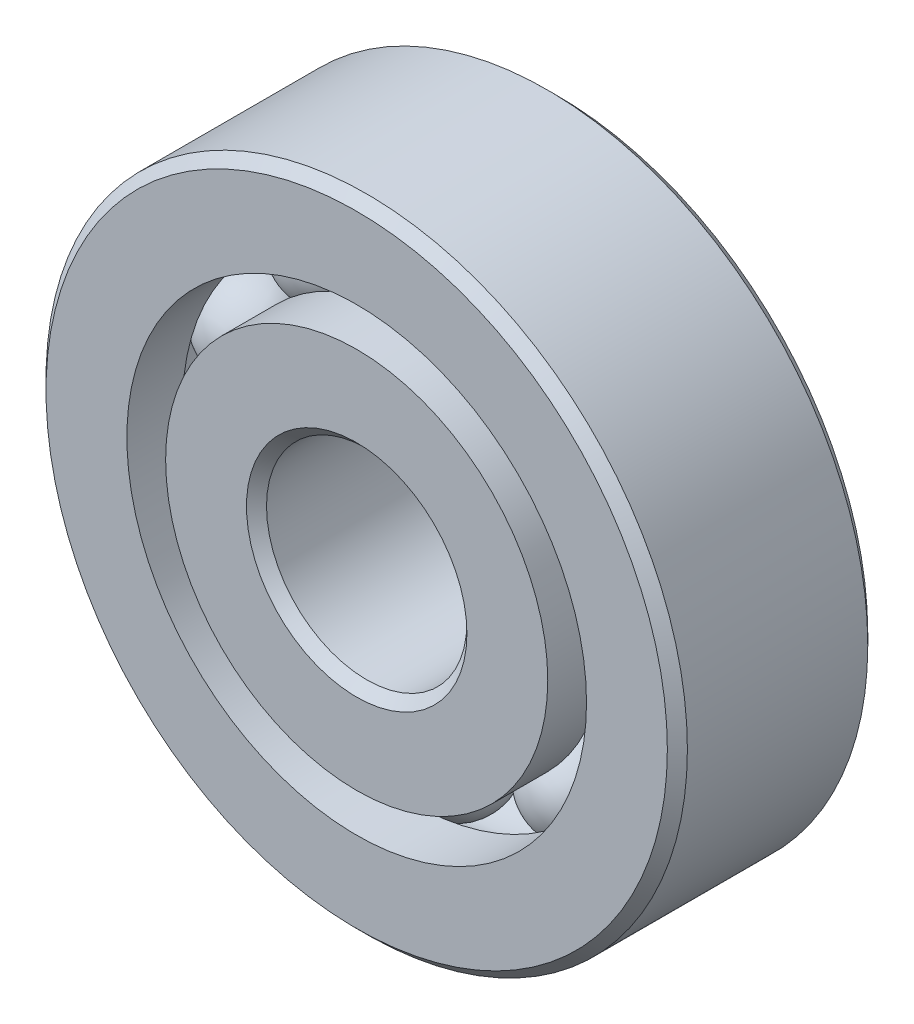
SolidWorks part; units mm, degrees
ref_plane "Front Plane" through (0, 0, 0) normal (0, 0, 1) x (1, 0, 0)
ref_plane "Top Plane" through (0, 0, 0) normal (0, 1, 0) x (1, 0, 0)
ref_plane "Right Plane" through (0, 0, 0) normal (1, 0, 0) x (0, 0, -1)
sketch "Sketch1" plane through (0, 0, 0) normal (1, 0, 0) x (0, 0, -1)
  line L0 (-2.5, 0) -> (2.5, 0) construction
  line L1 (0, 8) -> (0, -8) construction
  line L2 (2.25, 8) -> (-2.25, 8)
  line L3 (-2.25, 8) -> (-2.5, 7.75)
  line L4 (-2.5, 7.75) -> (-2.5, 5.7335)
  line L5 (-2.5, 5.7335) -> (-1.1111, 5.7335)
  line L6 (2.5, 5.7335) -> (1.1111, 5.7335)
  line L7 (2.5, 7.75) -> (2.5, 5.7335)
  line L8 (2.25, 8) -> (2.5, 7.75)
  line L9 (0, 8) -> (0, 5.25) construction
  line L10 (0, 5.25) -> (0, 2.5) construction
  arc A0 (-1.1111, 5.7335) -> (1.1111, 5.7335) centre (0, 5.25) cw
  point P14 (0, 2.5)
  dimension "Width" = 5
  dimension "OD" = 16
  dimension "D1" = 45
  dimension "D2" = 0.25
  dimension "Shaft Dia" = 5
  dimension "D3" = 2.2222
  dimension "D4" = 0.4835
revolve "Revolve1" add sketch "Sketch1" angle 360 about L0
sketch "Sketch3" plane through (0, 0, 0) normal (1, 0, 0) x (0, 0, -1)
  line L0 (-2.5, 4.7665) -> (-1.1111, 4.7665)
  line L1 (0, 8) -> (0, -8) construction
  line L2 (-2.5, 7.75) -> (-2.5, 5.7335) construction
  line L3 (-2.5, 4.7665) -> (-2.5, 2.75)
  line L4 (-2.25, 8) -> (-2.5, 7.75) construction
  line L5 (-2.5, 2.75) -> (-2.25, 2.5)
  line L6 (-2.25, 2.5) -> (2.25, 2.5)
  line L7 (2.25, 8) -> (2.25, -8) construction
  line L8 (2.25, 2.5) -> (2.5, 2.75)
  line L9 (2.5, -7.75) -> (2.5, 7.75) construction
  line L10 (2.5, 2.75) -> (2.5, 4.7665)
  line L11 (2.5, 4.7665) -> (1.1111, 4.7665)
  line L13 (2.25, 8) -> (2.5, 7.75) construction
  arc A0 (1.1111, 5.7335) -> (-1.1111, 5.7335) centre (0, 5.25) ccw construction
  arc A1 (1.1111, 4.7665) -> (-1.1111, 4.7665) centre (0, 5.25) cw
revolve "Revolve3" add sketch "Sketch3" angle 360 about L0
sketch "Sketch4" plane through (0, 0, 0) normal (1, 0, 0) x (0, 0, -1)
  line L0 (-1.2118, 5.25) -> (1.2118, 5.25)
  arc A2 (-1.2118, 5.25) -> (1.2118, 5.25) centre (0, 5.25) cw
  arc A3 (1.1111, 5.7335) -> (-1.1111, 5.7335) centre (0, 5.25) ccw construction
revolve "Revolve4" add sketch "Sketch4" angle 360 about L0
ref_axis "Axis1" through (0, 0, -2.5) along (0, 0, 1)
pattern_circular "CirPattern1" count 10 every 36 about axis through (0, 0, -2.5) along (0, 0, 1) of bodies 104
sketch "Sketch5" plane through (0, 0, 0) normal (1, 0, 0) x (0, 0, -1)
  line L0 (-2.5, 5.7335) -> (-1.1111, 5.7335) construction
  line L1 (-2.375, 5.7335) -> (-1.2118, 5.7335)
  line L2 (-2.375, 5.7335) -> (-2.375, 4.7665)
  line L3 (-2.375, 4.7665) -> (-1.2118, 4.7665)
  line L4 (-1.2118, 5.7335) -> (-1.2118, 4.7665)
  line L5 (-2.5, 4.7665) -> (-1.1111, 4.7665) construction
  line L6 (2.5, 5.7335) -> (1.1111, 5.7335) construction
  line L7 (2.375, 5.7335) -> (1.2118, 5.7335)
  line L8 (2.375, 5.7335) -> (2.375, 4.7665)
  line L9 (2.375, 4.7665) -> (1.2118, 4.7665)
  line L10 (1.2118, 5.7335) -> (1.2118, 4.7665)
  line L11 (2.5, 4.7665) -> (1.1111, 4.7665) construction
  line L12 (-2.25, 8) -> (-2.5, 7.75) construction
  point P18 (-2.375, 7.875)
revolve "Revolve5" [suppressed] add sketch "Sketch5" angle 360 about L0
equation "\"D2@Sketch1\" = \"Width@Sketch1\"*.05"
equation "\"D3@Sketch1\" = \"Width@Sketch1\"/2.25"
equation "\"D4@Sketch1\" = (((\"OD@Sketch1\"-\"Width@Sketch1\")/2)/3.25)/3.5"
equation "\"D2@CirPattern1\" = 360/\"Balls@CirPattern1\""
